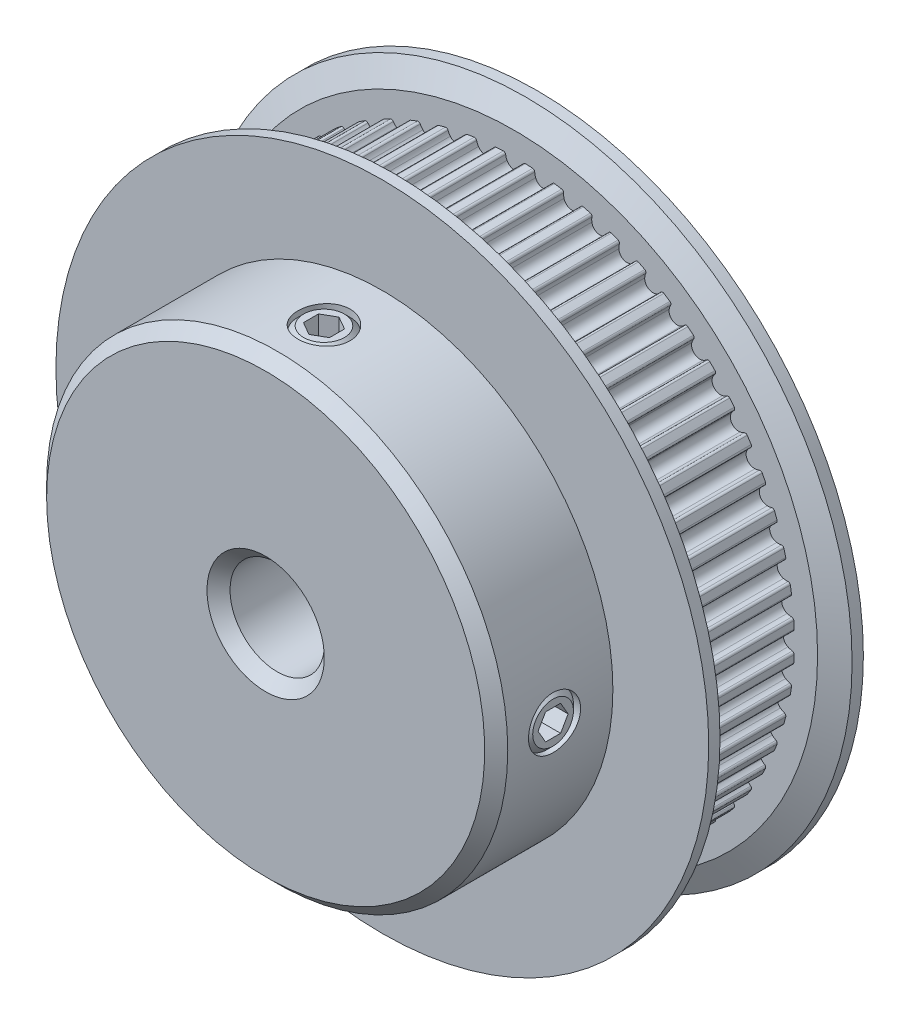
SolidWorks part; units mm, degrees
ref_plane "Front Plane" through (0, 0, 0) normal (0, 0, 1) x (1, 0, 0)
ref_plane "Top Plane" through (0, 0, 0) normal (0, 1, 0) x (1, 0, 0)
ref_plane "Right Plane" through (0, 0, 0) normal (1, 0, 0) x (0, 0, -1)
sketch "Sketch1" plane through (0, 0, 0) normal (0, 0, 1) x (1, 0, 0)
  line L1 (-1.9027, 18.097) -> (1.9027, 18.097) construction
  line L4 (0, 0) -> (0, 18.097) construction
  line L5 (0, 18.097) -> (0, 19.7068) construction
  line L6 (0, 19.101) -> (1.9973, 18.9963) construction
  line L7 (1.9973, 18.9963) -> (2.8966, 18.9017) construction
  line L8 (1.9973, 18.9963) -> (1.9027, 18.097) construction
  line L9 (-1.9973, 18.9963) -> (-1.9027, 18.097) construction
  line L10 (-1.9707, 18.7437) -> (-2.31, 21.971)
  line L11 (-2.31, 21.971) -> (2.31, 21.971)
  line L12 (2.31, 21.971) -> (1.9707, 18.7437)
  circle A0 centre (0, 0) radius 19.101 construction
  circle A1 centre (0, 0) radius 21.971 construction
  circle A2 centre (0, 0) radius 18.847 construction
  arc A3 (-0.4989, 18.4088) -> (0.4989, 18.4088) centre (0, 18.652) ccw
  arc A4 (-0.4989, 18.4088) -> (-0.5897, 18.7039) centre (0.4, 18.847) cw
  arc A5 (-1.9707, 18.7437) -> (-0.7441, 18.8323) centre (0, 0) cw
  arc A6 (-0.5897, 18.7039) -> (-0.7441, 18.8323) centre (-0.7382, 18.6824) ccw
  arc A7 (1.9707, 18.7437) -> (0.7441, 18.8323) centre (0, 0) ccw
  arc A8 (0.5897, 18.7039) -> (0.7441, 18.8323) centre (0.7382, 18.6824) cw
  arc A9 (0.4989, 18.4088) -> (0.5897, 18.7039) centre (-0.4, 18.847) ccw
  point P6 (0, 20.9083)
  point P11 (0, 19.101)
  point P13 (0, 21.971)
  point P14 (0, 18.847)
  dimension "D1" = 1.2015
  dimension "D2" = 0.6058
sketch "Sketch2" plane through (0, 0, 0) normal (1, 0, 0) x (0, 0, -1)
  line L0 (-9.1313, 3.175) -> (9.1313, 3.175)
  line L1 (-9.1313, 3.175) -> (-9.1313, 15.52)
  line L2 (-9.1313, 15.52) -> (-1.2787, 15.52)
  line L3 (-1.2787, 15.52) -> (-1.2787, 21.971)
  line L4 (-1.2787, 21.971) -> (0.2413, 21.971) construction
  line L5 (0.2413, 21.971) -> (0.2413, 18.847) construction
  line L6 (0.2413, 18.847) -> (7.6113, 18.847)
  line L7 (7.6113, 18.847) -> (7.6113, 21.971) construction
  line L8 (7.6113, 21.971) -> (9.1313, 21.971) construction
  line L9 (9.1313, 21.971) -> (9.1313, 3.175)
  line L10 (-9.1313, 0) -> (9.1313, 0) construction
  line L11 (8.3713, 21.971) -> (7.6113, 20.409)
  line L12 (0.2413, 20.409) -> (-0.5187, 21.971)
  line L13 (-1.2787, 21.971) -> (-0.5187, 21.971)
  line L14 (0.2413, 20.409) -> (0.2413, 18.847)
  line L15 (7.6113, 18.847) -> (7.6113, 20.409)
  line L16 (8.3713, 21.971) -> (9.1313, 21.971)
  arc A0 (0.2413, 20.409) -> (-0.5187, 21.971) centre (-1.7439, 20.409) ccw construction
  arc A1 (7.6113, 20.409) -> (8.3713, 21.971) centre (9.5965, 20.409) cw construction
  point P12 (0.2413, 20.409)
  point P14 (-0.5187, 21.971)
  point P20 (7.6113, 20.409)
  point P21 (8.3713, 21.971)
  point P25 (7.6113, 0)
  point P26 (0.2413, 0)
revolve "Revolve1" add sketch "Sketch2" angle 360 mid plane about L10
sketch "Sketch3" plane through (0, 0, 0) normal (0, 0, 1) x (1, 0, 0)
  line L6 (2.31, 21.971) -> (-2.31, 21.971)
  line L7 (1.9707, 18.7437) -> (2.31, 21.971)
  line L8 (-2.31, 21.971) -> (-1.9707, 18.7437)
  line L9 (2.31, 21.971) -> (-2.31, 21.971)
  line L10 (1.9707, 18.7437) -> (2.31, 21.971)
  line L11 (-2.31, 21.971) -> (-1.9707, 18.7437)
  arc A8 (1.9707, 18.7437) -> (0.7441, 18.8323) centre (0, 0) ccw
  arc A9 (0.7441, 18.8323) -> (0.5897, 18.7039) centre (0.7382, 18.6824) ccw
  arc A10 (0.4989, 18.4088) -> (0.5897, 18.7039) centre (-0.4, 18.847) ccw
  arc A11 (-0.4989, 18.4088) -> (0.4989, 18.4088) centre (0, 18.652) ccw
  arc A12 (-0.5897, 18.7039) -> (-0.4989, 18.4088) centre (0.4, 18.847) ccw
  arc A13 (-0.5897, 18.7039) -> (-0.7441, 18.8323) centre (-0.7382, 18.6824) ccw
  arc A14 (-0.7441, 18.8323) -> (-1.9707, 18.7437) centre (0, 0) ccw
  arc A15 (1.9707, 18.7437) -> (0.7441, 18.8323) centre (0, 0) ccw
  arc A16 (0.7441, 18.8323) -> (0.5897, 18.7039) centre (0.7382, 18.6824) ccw
  arc A17 (0.4989, 18.4088) -> (0.5897, 18.7039) centre (-0.4, 18.847) ccw
  arc A18 (-0.4989, 18.4088) -> (0.4989, 18.4088) centre (0, 18.652) ccw
  arc A19 (-0.5897, 18.7039) -> (-0.4989, 18.4088) centre (0.4, 18.847) ccw
  arc A20 (-0.5897, 18.7039) -> (-0.7441, 18.8323) centre (-0.7382, 18.6824) ccw
  arc A21 (-0.7441, 18.8323) -> (-1.9707, 18.7437) centre (0, 0) ccw
  dimension "D1" = 0
extrude "Cut-Extrude1" cut sketch "Sketch3" against normal up to vertex (7.6113 mm away) from vertex up to point (0, 18.847, -7.6113) starting at point (0, 18.847, -0.2413)
pattern_circular "CirPattern1" count 60 over 360 about axis through (0, 0, 9.1313) along (0, 0, 1) of "Cut-Extrude1"
sketch "Sketch4" plane through (0, 0, 0) normal (1, 0, 0) x (0, -1, 0)
  line L0 (0, -1.2787) -> (0, -9.1313) construction
  line L1 (-15.52, -1.2787) -> (15.52, -1.2787) construction
  line L2 (-15.52, -9.1313) -> (15.52, -9.1313) construction
  circle A0 centre (0, -5.205) radius 1.7526
extrude "Cut-Extrude2" cut sketch "Sketch4" along normal through all
ref_plane "Plane1" through (0, 0, 5.205) normal (0, 0, 1) x (1, 0, 0)
sketch "Sketch5" plane through (0, 0, 5.205) normal (0, 0, 1) x (1, 0, 0)
  line L0 (0, 0.1664) -> (0, 15.52) construction
  line L1 (3.175, -1.3716) -> (3.175, 0)
  line L2 (3.556, -1.7526) -> (15.0397, -1.7526)
  line L3 (3.175, 0) -> (15.52, 0) construction
  line L4 (3.175, 0) -> (15.4207, 0)
  line L5 (15.4207, 0) -> (15.4207, -1.3716)
  line L6 (3.556, -1.7526) -> (3.175, -1.3716)
  line L7 (15.4207, -1.3716) -> (15.0397, -1.7526)
  circle A0 centre (0, 0) radius 15.52 construction
  circle A1 centre (0, 0) radius 3.175 construction
  point P2 (3.175, -1.7526)
  point P11 (15.4207, -1.7526)
revolve "Revolve2" add sketch "Sketch5" angle 360 mid plane about L4
sketch "Sketch6" plane through (15.4207, 5.3841, 0) normal (-1, 0, 0) x (0, -1, 0)
  line L1 (5.3841, 6.2169) -> (4.5078, 5.7109)
  line L2 (4.5078, 5.7109) -> (4.5078, 4.6991)
  line L3 (4.5078, 4.6991) -> (5.3841, 4.1931)
  line L4 (5.3841, 4.1931) -> (6.2604, 4.6991)
  line L5 (6.2604, 4.6991) -> (6.2604, 5.7109)
  line L6 (6.2604, 5.7109) -> (5.3841, 6.2169)
  circle A0 centre (5.3841, 5.205) radius 0.8763 construction
  dimension "D1" = 1.7526
extrude "Cut-Extrude3" cut sketch "Sketch6" along normal blind 1.3144
pattern_circular "CirPattern2" count 2 over 90 about axis through (0, 0, 9.1313) along (0, 0, 1) of "Cut-Extrude2", "Revolve2", "Cut-Extrude3"
chamfer "Chamfer1" distance 0.776 angle 45 2 edges at (3.175, 0, 9.1313) (15.52, 0, 9.1313)
ref_axis "Center Axis 1" through (0, 0, -9.1313) along (0, 0, 1)
ref_plane "Contact Plane 1" through (0, 0, 9.1313) normal (0, 0, 1) x (1, 0, 0)
ref_plane "Contact Plane 2" through (0, 0, -9.1313) normal (0, 0, -1) x (-1, 0, 0)
equation "\"D2@Sketch1\" = \"D1@Sketch1\"/2"
equation "\"D1@Sketch6\" = \"Set Screw@Sketch4\" / 2"
equation "\"D1@Cut-Extrude3\" = \"D1@Sketch6\"*.75"
equation "\"D1@Chamfer1\"=\"Hub Dia@Sketch2\"*.025"
